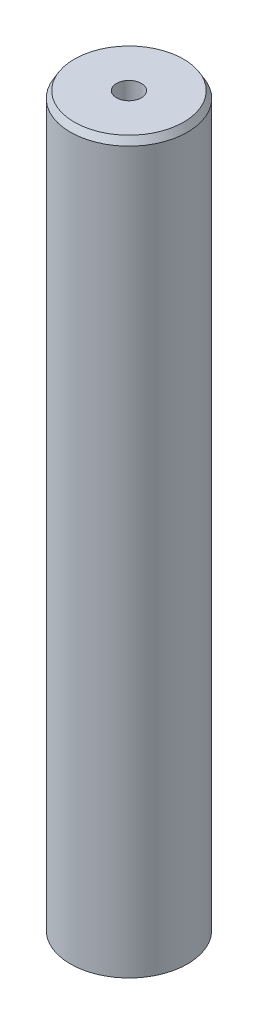
SolidWorks part; units mm, degrees
ref_plane "Front Plane" through (0, 0, 0) normal (0, 0, 1) x (1, 0, 0)
ref_plane "Top Plane" through (0, 0, 0) normal (0, 1, 0) x (1, 0, 0)
ref_plane "Right Plane" through (0, 0, 0) normal (1, 0, 0) x (0, 0, -1)
sketch "Sketch1" plane through (0, 0, 0) normal (0, 1, 0) x (1, 0, 0)
  circle A0 centre (0, 0) radius 5
  dimension "SHAFT_OD" = 10
extrude "Boss-Extrude1" add sketch "Sketch1" along normal blind 62.4386
sketch "Sketch2" plane through (0, 0, 0) normal (0, 1, 0) x (1, 0, 0)
  circle A0 centre (0, 0) radius 1.0652
  dimension "BORE_D" = 2.1303
extrude "Cut-Extrude1" cut sketch "Sketch2" along normal through all
chamfer "Chamfer1" distance 0.5762 angle 30 2 edges at (0, 62.4386, 5) (0, 0, 5) first distance on face at (0, 62.4386, 5) first distance on face at (0, 0, 1.0652)
